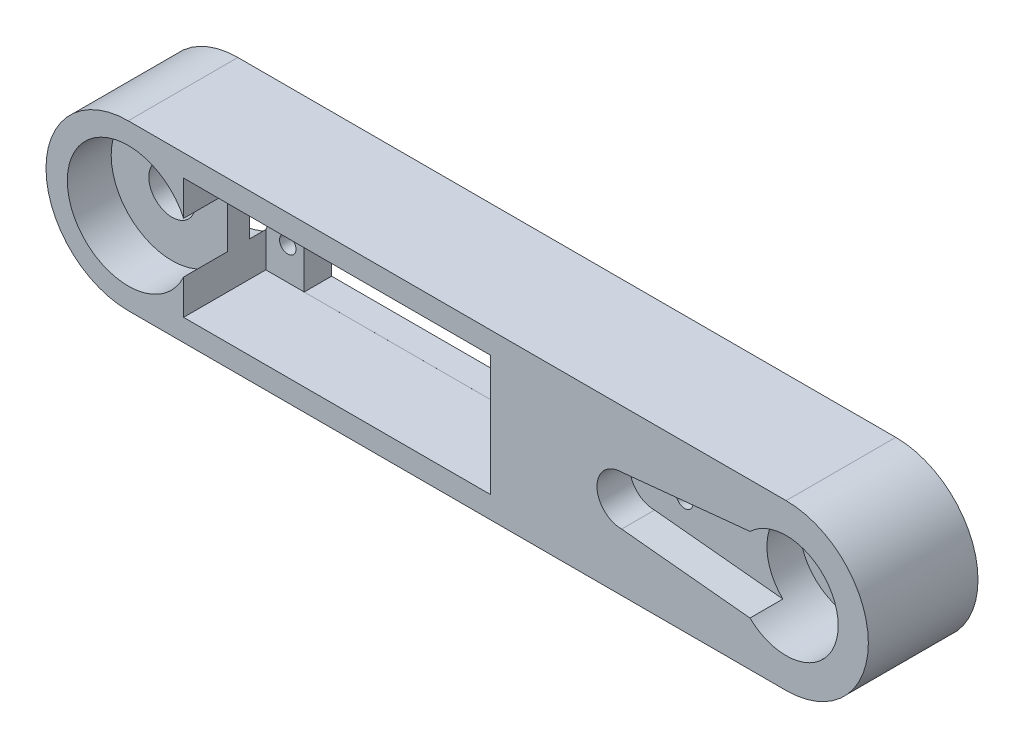
SolidWorks part; units mm, degrees
ref_plane "Front Plane" through (0, 0, 0) normal (0, 0, 1) x (1, 0, 0)
ref_plane "Top Plane" through (0, 0, 0) normal (0, 1, 0) x (1, 0, 0)
ref_plane "Right Plane" through (0, 0, 0) normal (1, 0, 0) x (0, 0, -1)
sketch "Sketch1" plane through (0, 0, 0) normal (0, 0, 1) x (1, 0, 0)
  line L0 (0, 0) -> (120, 0) construction
  line L1 (0, 15) -> (120, 15)
  line L2 (0, -15) -> (120, -15)
  circle A0 centre (0, 0) radius 15
  circle A1 centre (120, 0) radius 15
  dimension "D1" = 30
  dimension "D2" = 120
extrude "Boss-Extrude1" add sketch "Sketch1" along normal mid plane 20 contours A0 | A0 L0 A1 L1 | L0 A0 L2 A1 | A1 region at (60, 7.777, 0) region at (10.3066, -10.3066, 0) region at (60, -7.777, 0) region at (109.6934, 10.3066, 0)
sketch "Sketch3" plane through (0, 0, 10) normal (0, 0, 1) x (1, 0, 0)
  line L0 (0, 0) -> (94, 0) construction
  line L1 (90, 4.5) -> (120, 7.5)
  line L2 (90, -4.5) -> (120, -7.5)
  circle A0 centre (120, 0) radius 7.5
  circle A1 centre (90, 0) radius 4.5
  circle A2 centre (95.5, 0) radius 1.5
  circle A3 centre (120, 0) radius 4.25
  dimension "D2" = 15
  dimension "D3" = 9
  dimension "D5" = 3
  dimension "D7" = 8.5
  dimension "D1" = 120
  dimension "D4" = 30
  dimension "D6" = 24.5
extrude "Cut-Extrude4" cut sketch "Sketch3" against normal blind 6 contours A1 L0 A2 | L0 A1 A2 | A2 A1 L2 A0 L1 region at (89.9534, 1.9265, 10) region at (89.9534, -1.9265, 10) region at (104.4995, 0, 10)
extrude "Cut-Extrude5" cut sketch "Sketch3<3>" against normal blind 12 contours A1 A2 | A1 A2 | L1 A0 L2 A3 region at (119.2785, 7.2147, 10) region at (95.6315, 0, 10) region at (94.2749, 0, 10)
sketch "Sketch3<3>" plane through (0, 0, 10) normal (0, 0, 1) x (1, 0, 0) same geometry as "Sketch3"
extrude "Cut-Extrude6" cut sketch "Sketch3<4>" against normal through all contours A3 region at (120, 0, 10)
sketch "Sketch3<4>" plane through (0, 0, 10) normal (0, 0, 1) x (1, 0, 0) same geometry as "Sketch3"
sketch "Sketch4" plane through (0, 0, 10) normal (0, 0, 1) x (1, 0, 0)
  line L0 (0, 0) -> (120, 0) construction
  line L2 (59.1, -11) -> (17.1, -11)
  line L3 (59.1, -11) -> (59.1, 11)
  line L4 (59.1, 11) -> (17.1, 11)
  line L5 (17.1, -11) -> (17.1, 11)
  line L6 (59.1, -11) -> (17.1, 11) construction
  line L7 (59.1, 11) -> (17.1, -11) construction
  circle A0 centre (0, 0) radius 4.25
  circle A1 centre (0, 0) radius 11.11
  circle A2 centre (27.1, 0) radius 2.6569
  point P4 (38.1, 0)
  dimension "D3" = 8.5
  dimension "D4" = 22.22
  dimension "D1" = 22
  dimension "D2" = 42
  dimension "D5" = 27.1
  dimension "D6" = 10
extrude "Cut-Extrude8" cut sketch "Sketch4" against normal through all contours A0 | L3 L2 L5 L4
sketch "Sketch5" plane through (0, 0, -10) normal (0, 0, -1) x (-1, 0, 0)
  circle A0 centre (0, 0) radius 11.11
  dimension "D1" = 22.22
extrude "Cut-Extrude10" cut sketch "Sketch5" against normal blind 8
mirror "Mirror2" about plane through (0, 0, 0) normal (0, 0, 1) of "Cut-Extrude10"
sketch "Sketch7" plane through (0, 0, 10) normal (0, 0, 1) x (1, 0, 0)
  line L0 (38.1, 11) -> (38.1, -11) construction
  line L1 (59.1, 11) -> (17.1, 11) construction
  line L2 (59.1, -11) -> (17.1, -11) construction
  line L4 (66.1, -11.0014) -> (10.1, -11.0014)
  line L5 (66.1, -11.0014) -> (66.1, 11.0014)
  line L6 (66.1, 11.0014) -> (10.1, 11.0014)
  line L7 (10.1, -11.0014) -> (10.1, 11.0014)
  line L8 (66.1, -11.0014) -> (10.1, 11.0014) construction
  line L9 (66.1, 11.0014) -> (10.1, -11.0014) construction
  point P6 (38.1, 0)
  dimension "D2" = 56
extrude "Cut-Extrude12" cut sketch "Sketch7" against normal blind 15
sketch "Sketch8" plane through (0, 0, -5) normal (0, 0, 1) x (1, 0, 0)
  line L0 (38.1, 11.0014) -> (38.1, -11.0014) construction
  line L1 (66.1, 11.0014) -> (10.1, 11.0014) construction
  line L2 (10.1, -11.0014) -> (66.1, -11.0014) construction
  line L3 (14.1, 5) -> (14.1, -5) construction
  line L4 (62.1, 5) -> (62.1, -5) construction
  line L5 (38.1, 0) -> (25.4065, 0) construction
  line L6 (14.1, 0) -> (20.8073, 0) construction
  circle A0 centre (14.1, 5) radius 1.5
  circle A1 centre (14.1, -5) radius 1.5
  circle A2 centre (62.1, -5) radius 1.5
  circle A3 centre (62.1, 5) radius 1.5
  dimension "D1" = 3
  dimension "D2" = 10
  dimension "D3" = 48
extrude "Cut-Extrude13" cut sketch "Sketch8" against normal blind 14 contours A0 | A1 | A2 | A3 region at (14.1, 5, -5) region at (14.1, -5, -5) region at (62.1, -5, -5)
sketch "Sketch9" plane through (0, 0, 10) normal (0, 0, 1) x (1, 0, 0)
  circle A0 centre (120, 0) radius 9.5
  dimension "D1" = 19
extrude "Cut-Extrude14" cut sketch "Sketch9" against normal up to surface (12 mm away) up to face at (124.25, 0, -2)
sketch "Sketch10" plane through (0, 0, -10) normal (0, 0, -1) x (-1, 0, 0)
  circle A0 centre (-62.1, 5) radius 3.5
  circle A1 centre (-62.1, -5) radius 3.5
  circle A2 centre (-14.1, 5) radius 3.5
  circle A3 centre (-14.1, -5) radius 3.5
  dimension "D1" = 7
